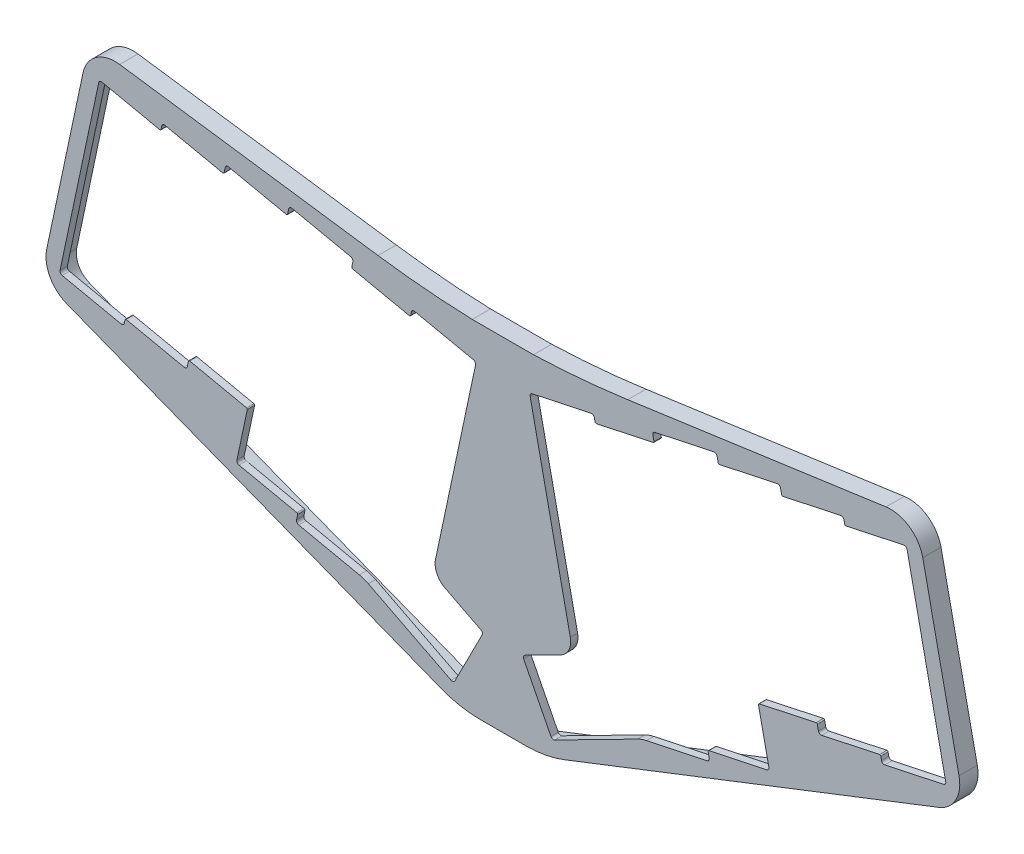
SolidWorks part; units mm, degrees
ref_plane "Front Plane" through (0, 0, 0) normal (0, 0, 1) x (1, 0, 0)
ref_plane "Top Plane" through (0, 0, 0) normal (0, 1, 0) x (1, 0, 0)
ref_plane "Right Plane" through (0, 0, 0) normal (1, 0, 0) x (0, 0, -1)
sketch "Model" plane through (0, 0, 0) normal (0, 0, 1) x (1, 0, 0)
  line L0 (154.4838, -20.4293) -> (153.8335, -20.5675)
  line L1 (132.561, -4.6423) -> (132.9485, -6.4654)
  line L2 (96.3912, -4.6423) -> (96.0037, -6.4654)
  line L3 (74.4684, -20.4293) -> (75.1187, -20.5675)
  line L4 (190.9006, 56.3705) -> (190.5991, 57.7888)
  line L5 (189.7096, 58.3664) -> (173.8636, 54.9983)
  line L6 (207.1024, 59.5076) -> (191.2564, 56.1394)
  line L7 (173.2063, 56.6477) -> (173.5078, 55.2294)
  line L8 (156.1773, 53.7948) -> (172.3167, 57.2253)
  line L9 (155.5996, 52.9053) -> (155.9011, 51.4869)
  line L10 (140.1175, 47.8253) -> (155.67, 51.1311)
  line L11 (139.5641, 48.9856) -> (139.7617, 48.0564)
  line L12 (122.5352, 46.1328) -> (138.6746, 49.5633)
  line L13 (130.551, 4.8138) -> (121.9574, 45.2436)
  line L14 (132.561, -4.6423) -> (130.551, 4.8138)
  line L15 (120.4913, -16.9719) -> (130.3277, -11.96)
  line L16 (127.6544, -32.6822) -> (120.1636, -17.9806)
  line L17 (151.3727, -21.4389) -> (128.6628, -33.0102)
  line L18 (154.4838, -20.4293) -> (170.4653, -17.0323)
  line L19 (171.043, -16.1428) -> (170.7415, -14.7244)
  line L20 (186.8186, -11.0005) -> (170.9726, -14.3686)
  line L21 (187.3963, -10.1109) -> (184.5479, 3.2897)
  line L22 (200.3315, 6.9513) -> (184.7789, 3.6455)
  line L23 (200.6873, 6.7203) -> (200.9888, 5.3019)
  line L24 (218.2776, 6.9321) -> (218.0801, 7.8614)
  line L25 (201.8783, 4.7243) -> (217.7243, 8.0924)
  line L26 (227.8628, 8.2028) -> (219.1672, 6.3544)
  line L27 (235.3066, 9.785) -> (227.8628, 8.2028)
  line L28 (38.0516, 56.3705) -> (38.3531, 57.7888)
  line L29 (39.2426, 58.3664) -> (55.0886, 54.9983)
  line L30 (4.5609, 61.1377) -> (20.4069, 57.7696)
  line L31 (20.9602, 58.9299) -> (20.7627, 58.0006)
  line L32 (21.8498, 59.5076) -> (37.6958, 56.1394)
  line L33 (55.7459, 56.6477) -> (55.4444, 55.2294)
  line L34 (72.7749, 53.7948) -> (56.6354, 57.2253)
  line L35 (73.3526, 52.9053) -> (73.0511, 51.4869)
  line L36 (88.8347, 47.8253) -> (73.2821, 51.1311)
  line L37 (89.388, 48.9856) -> (89.1905, 48.0564)
  line L38 (106.417, 46.1328) -> (90.2776, 49.5633)
  line L39 (98.4012, 4.8138) -> (106.9948, 45.2436)
  line L40 (96.3912, -4.6423) -> (98.4012, 4.8138)
  line L41 (108.4608, -16.9719) -> (98.6245, -11.96)
  line L42 (101.2978, -32.6822) -> (108.7886, -17.9806)
  line L43 (77.5795, -21.4389) -> (100.2893, -33.0102)
  line L44 (74.4684, -20.4293) -> (58.4869, -17.0323)
  line L45 (57.9092, -16.1428) -> (58.2107, -14.7244)
  line L46 (42.1336, -11.0005) -> (57.9796, -14.3686)
  line L47 (41.5559, -10.1109) -> (44.4043, 3.2897)
  line L48 (28.6207, 6.9513) -> (44.1732, 3.6455)
  line L49 (28.2649, 6.7203) -> (27.9634, 5.3019)
  line L50 (10.6745, 6.9321) -> (10.872, 7.8614)
  line L51 (27.0739, 4.7243) -> (11.2279, 8.0924)
  line L52 (1.0894, 8.2028) -> (9.785, 6.3544)
  line L53 (-6.3544, 9.785) -> (1.0894, 8.2028)
  line L54 (-6.861, 11.0092) -> (-6.9321, 10.6744)
  line L55 (3.6714, 60.5601) -> (-6.861, 11.0092)
  line L56 (120.9761, -36.0417) -> (122.177, -36.0417)
  line L57 (120.9761, -36.4417) -> (122.177, -36.4417)
  line L58 (107.9761, -36.0417) -> (106.7752, -36.0417)
  line L59 (107.9761, -36.4417) -> (106.7752, -36.4417)
  line L60 (119.4761, -36.0417) -> (120.9761, -36.0417)
  line L61 (119.4761, -36.4417) -> (120.9761, -36.4417)
  line L62 (109.4761, -36.0417) -> (107.9761, -36.0417)
  line L63 (109.4761, -36.4417) -> (107.9761, -36.4417)
  line L64 (130.1088, -33.2876) -> (123.8474, -35.7278)
  line L65 (130.2541, -33.6603) -> (123.9926, -36.1005)
  line L66 (98.8433, -33.2876) -> (105.1048, -35.7278)
  line L67 (98.6981, -33.6603) -> (104.9596, -36.1005)
  line L68 (114.4761, -36.0417) -> (119.4761, -36.0417)
  line L69 (114.4761, -36.4417) -> (119.4761, -36.4417)
  line L70 (114.4761, -36.0417) -> (109.4761, -36.0417)
  line L71 (114.4761, -36.4417) -> (109.4761, -36.4417)
  line L72 (108.1261, 52.202) -> (120.8261, 52.202)
  line L73 (108.1261, 52.602) -> (120.8261, 52.602)
  line L74 (106.0842, 55.5642) -> (122.868, 55.5642)
  line L75 (80.2395, 57.8151) -> (9.4178, 67.7684)
  line L76 (-0.6381, 60.7272) -> (-10.5878, 13.9175)
  line L77 (-5.0525, 3.6606) -> (97.6451, -36.3623)
  line L78 (108.1754, -38.3417) -> (114.4761, -38.3417)
  line L79 (114.4761, -38.3417) -> (120.7768, -38.3417)
  line L80 (131.3071, -36.3623) -> (234.0046, 3.6606)
  line L81 (239.5399, 13.9175) -> (229.5902, 60.7272)
  line L82 (219.5343, 67.7684) -> (148.7127, 57.8151)
  line L83 (130.1088, -33.2876) -> (232.8064, 6.7354)
  line L84 (236.312, 13.2314) -> (226.3623, 60.0411)
  line L85 (219.9936, 64.5005) -> (149.1719, 54.5472)
  line L86 (130.2541, -33.6603) -> (232.9516, 6.3627)
  line L87 (236.7033, 13.3146) -> (226.7536, 60.1242)
  line L88 (219.9379, 64.8966) -> (149.1163, 54.9433)
  line L89 (79.7802, 54.5472) -> (8.9586, 64.5005)
  line L90 (2.5898, 60.0411) -> (-7.3599, 13.2314)
  line L91 (-3.8542, 6.7354) -> (98.8433, -33.2876)
  line L92 (79.8359, 54.9433) -> (9.0142, 64.8966)
  line L93 (2.1986, 60.1242) -> (-7.7511, 13.3146)
  line L94 (-3.9994, 6.3627) -> (98.6981, -33.6603)
  line L95 (224.3913, 61.1377) -> (208.5453, 57.7696)
  line L96 (207.9919, 58.9299) -> (208.1894, 58.0006)
  line L97 (235.8132, 11.0092) -> (235.8843, 10.6744)
  line L98 (225.2808, 60.5601) -> (235.8132, 11.0092)
  line L99 (108.1159, 52.2022) -> (108.1261, 52.202)
  line L100 (120.8261, 52.202) -> (120.8363, 52.2022)
  arc A0 (130.3277, -11.96) -> (132.9485, -6.4654) centre (128.0578, -7.505) ccw
  arc A1 (153.8335, -20.5675) -> (151.3727, -21.4389) centre (155.9126, -30.349) ccw
  arc A2 (96.0037, -6.4654) -> (98.6245, -11.96) centre (100.8944, -7.505) ccw
  arc A3 (77.5795, -21.4389) -> (75.1187, -20.5675) centre (73.0396, -30.349) ccw
  circle A4 centre (210.5718, 3.5051) radius 1
  circle A5 centre (147.4779, 51.4345) radius 1
  circle A6 centre (114.4761, 38.421) radius 1
  circle A7 centre (114.4761, -18.3417) radius 1
  circle A8 centre (81.4742, 51.4345) radius 1
  circle A9 centre (18.3804, 3.5051) radius 1
  circle A10 centre (13.0465, 61.3788) radius 1
  arc A11 (190.5991, 57.7888) -> (189.7096, 58.3664) centre (189.8655, 57.6328) ccw
  arc A12 (173.5078, 55.2294) -> (173.8636, 54.9983) centre (173.8012, 55.2917) ccw
  arc A13 (190.9006, 56.3705) -> (191.2564, 56.1394) centre (191.194, 56.4328) ccw
  arc A14 (155.67, 51.1311) -> (155.9011, 51.4869) centre (155.6077, 51.4246) ccw
  arc A15 (139.7617, 48.0564) -> (140.1175, 47.8253) centre (140.0551, 48.1188) ccw
  arc A16 (173.2063, 56.6477) -> (172.3167, 57.2253) centre (172.4727, 56.4917) ccw
  arc A17 (156.1773, 53.7948) -> (155.5996, 52.9053) centre (156.3332, 53.0612) ccw
  arc A18 (139.5641, 48.9856) -> (138.6746, 49.5633) centre (138.8305, 48.8297) ccw
  arc A19 (122.5352, 46.1328) -> (121.9574, 45.2436) centre (122.6911, 45.3992) ccw
  arc A20 (120.4913, -16.9719) -> (120.1636, -17.9806) centre (120.8318, -17.6401) ccw
  arc A21 (127.6544, -32.6822) -> (128.6628, -33.0102) centre (128.3227, -32.3417) ccw
  arc A22 (170.9726, -14.3686) -> (170.7415, -14.7244) centre (171.035, -14.6621) ccw
  arc A23 (184.7789, 3.6455) -> (184.5479, 3.2897) centre (184.8413, 3.3521) ccw
  arc A24 (200.6873, 6.7203) -> (200.3315, 6.9513) centre (200.3939, 6.6579) ccw
  arc A25 (170.4653, -17.0323) -> (171.043, -16.1428) centre (170.3094, -16.2987) ccw
  arc A26 (186.8186, -11.0005) -> (187.3963, -10.1109) centre (186.6626, -10.2668) ccw
  arc A27 (218.0801, 7.8614) -> (217.7243, 8.0924) centre (217.7867, 7.799) ccw
  arc A28 (200.9888, 5.3019) -> (201.8783, 4.7243) centre (201.7224, 5.4579) ccw
  arc A29 (218.2776, 6.9321) -> (219.1672, 6.3544) centre (219.0113, 7.0881) ccw
  arc A30 (39.2426, 58.3664) -> (38.3531, 57.7888) centre (39.0867, 57.6328) ccw
  arc A31 (55.0886, 54.9983) -> (55.4444, 55.2294) centre (55.151, 55.2917) ccw
  arc A32 (37.6958, 56.1394) -> (38.0516, 56.3705) centre (37.7582, 56.4328) ccw
  arc A33 (20.4069, 57.7696) -> (20.7627, 58.0006) centre (20.4693, 58.063) ccw
  arc A34 (73.0511, 51.4869) -> (73.2821, 51.1311) centre (73.3445, 51.4246) ccw
  arc A35 (88.8347, 47.8253) -> (89.1905, 48.0564) centre (88.8971, 48.1188) ccw
  arc A36 (4.5609, 61.1377) -> (3.6714, 60.5601) centre (4.405, 60.4041) ccw
  arc A37 (21.8498, 59.5076) -> (20.9602, 58.9299) centre (21.6939, 58.7739) ccw
  arc A38 (56.6354, 57.2253) -> (55.7459, 56.6477) centre (56.4795, 56.4917) ccw
  arc A39 (73.3526, 52.9053) -> (72.7749, 53.7948) centre (72.6189, 53.0612) ccw
  arc A40 (90.2776, 49.5633) -> (89.388, 48.9856) centre (90.1216, 48.8297) ccw
  arc A41 (106.9948, 45.2436) -> (106.417, 46.1328) centre (106.2611, 45.3992) ccw
  arc A42 (108.7886, -17.9806) -> (108.4608, -16.9719) centre (108.1204, -17.6401) ccw
  arc A43 (100.2893, -33.0102) -> (101.2978, -32.6822) centre (100.6295, -32.3417) ccw
  arc A44 (58.2107, -14.7244) -> (57.9796, -14.3686) centre (57.9172, -14.6621) ccw
  arc A45 (44.4043, 3.2897) -> (44.1732, 3.6455) centre (44.1109, 3.3521) ccw
  arc A46 (28.6207, 6.9513) -> (28.2649, 6.7203) centre (28.5583, 6.6579) ccw
  arc A47 (57.9092, -16.1428) -> (58.4869, -17.0323) centre (58.6428, -16.2987) ccw
  arc A48 (41.5559, -10.1109) -> (42.1336, -11.0005) centre (42.2895, -10.2668) ccw
  arc A49 (11.2279, 8.0924) -> (10.872, 7.8614) centre (11.1655, 7.799) ccw
  arc A50 (27.0739, 4.7243) -> (27.9634, 5.3019) centre (27.2298, 5.4579) ccw
  arc A51 (9.785, 6.3544) -> (10.6745, 6.9321) centre (9.9409, 7.0881) ccw
  arc A52 (-6.9321, 10.6744) -> (-6.3544, 9.785) centre (-6.1985, 10.5186) ccw
  arc A53 (122.177, -36.0417) -> (123.8474, -35.7278) centre (122.177, -31.4417) ccw
  arc A54 (122.177, -36.4417) -> (123.9926, -36.1005) centre (122.177, -31.4417) ccw
  arc A55 (105.1048, -35.7278) -> (106.7752, -36.0417) centre (106.7752, -31.4417) ccw
  arc A56 (104.9596, -36.1005) -> (106.7752, -36.4417) centre (106.7752, -31.4417) ccw
  circle A57 centre (215.9057, 61.3788) radius 1
  arc A58 (208.1894, 58.0006) -> (208.5453, 57.7696) centre (208.4829, 58.063) ccw
  arc A59 (225.2808, 60.5601) -> (224.3913, 61.1377) centre (224.5472, 60.4041) ccw
  arc A60 (207.9919, 58.9299) -> (207.1024, 59.5076) centre (207.2583, 58.7739) ccw
  arc A61 (235.3066, 9.785) -> (235.8843, 10.6744) centre (235.1507, 10.5186) ccw
  arc A62 (80.2395, 57.8151) -> (106.0842, 55.5642) centre (114.4761, 301.421) ccw
  arc A63 (9.4178, 67.7684) -> (-0.6381, 60.7272) centre (8.1653, 58.856) ccw
  arc A64 (-10.5878, 13.9175) -> (-5.0525, 3.6606) centre (-1.7844, 12.0463) ccw
  arc A65 (97.6451, -36.3623) -> (108.1754, -38.3417) centre (108.1754, -9.3417) ccw
  arc A66 (120.7768, -38.3417) -> (131.3071, -36.3623) centre (120.7768, -9.3417) ccw
  arc A67 (234.0046, 3.6606) -> (239.5399, 13.9175) centre (230.7366, 12.0463) ccw
  arc A68 (229.5902, 60.7272) -> (219.5343, 67.7684) centre (220.7869, 58.856) ccw
  arc A69 (122.868, 55.5642) -> (148.7127, 57.8151) centre (114.4761, 301.421) ccw
  arc A70 (232.8064, 6.7354) -> (236.312, 13.2314) centre (230.7366, 12.0463) ccw
  arc A71 (226.3623, 60.0411) -> (219.9936, 64.5005) centre (220.7869, 58.856) ccw
  arc A72 (120.8363, 52.2022) -> (149.1719, 54.5472) centre (114.4761, 301.421) ccw
  arc A73 (232.9516, 6.3627) -> (236.7033, 13.3146) centre (230.7366, 12.0463) ccw
  arc A74 (226.7536, 60.1242) -> (219.9379, 64.8966) centre (220.7869, 58.856) ccw
  arc A75 (120.8261, 52.602) -> (149.1163, 54.9433) centre (114.4761, 301.421) ccw
  arc A76 (79.7802, 54.5472) -> (108.1159, 52.2022) centre (114.4761, 301.421) ccw
  arc A77 (8.9586, 64.5005) -> (2.5898, 60.0411) centre (8.1653, 58.856) ccw
  arc A78 (-7.3599, 13.2314) -> (-3.8542, 6.7354) centre (-1.7844, 12.0463) ccw
  arc A79 (79.8359, 54.9433) -> (108.1261, 52.602) centre (114.4761, 301.421) ccw
  arc A80 (9.0142, 64.8966) -> (2.1986, 60.1242) centre (8.1653, 58.856) ccw
  arc A81 (-7.7511, 13.3146) -> (-3.9994, 6.3627) centre (-1.7844, 12.0463) ccw
extrude "Boss-Extrude1" add sketch "Model" along normal blind 2 contours A69 L74 A62 L75 A63 L76 A64 L77 A65 L78 L79 A66 L80 A67 L81 A68 L82 A81 L93 A80 L92 A79 L73 A75 L88 A74 L87 A73 L86 L65 A54 L57 L61 L69 L71 L63 L59 A56 L67 L94 | A9 | A10 | A7 | A6 | A5 | A57 | A4 | A8 | L90 A78 L91 L66 A55 L58 L62 L70 L68 L60 L56 A53 L64 L83 A70 L84 A71 L85 A72 L100 L72 L99 A76 L89 A77 A4 A5 A6 A7 A8 A9 A10 A52 L54 L55 A36 L30 A33 L31 A37 L32 A32 L28 | L93 A81 L94 L67 A56 L59 L63 L71 L69 L61 L57 A54 L65 L86 A73 L87 A74 L88 A75 L73 A79 L92 A80 A78 L90 A77 L89 A76 L99 L72 L100 A72 L85 A71 L84 A70 L83 L64 A53 L56 L60 L68 L70 L62 L58 A55 L66 L91 region at (114.4761, 12.873, 0) region at (120.2261, -36.1768, 0) region at (114.4761, 52.8432, 0) region at (210.5718, 3.5051, 0) region at (147.4779, 51.4345, 0) region at (114.4761, 38.421, 0) region at (114.4761, -18.3417, 0) region at (81.4742, 51.4345, 0) region at (18.3804, 3.5051, 0) region at (13.0465, 61.3788, 0) region at (215.9057, 61.3788, 0)
extrude "Boss-Extrude2" add sketch "Model<6>" against normal blind 3 contours L93 A81 L94 L67 A56 L59 L63 L71 L69 L61 L57 A54 L65 L86 A73 L87 A74 L88 A75 L73 A79 L92 A80 A78 L90 A77 L89 A76 L99 L72 L100 A72 L85 A71 L84 A70 L83 L64 A53 L56 L60 L68 L70 L62 L58 A55 L66 L91 | A69 L74 A62 L75 A63 L76 A64 L77 A65 L78 L79 A66 L80 A67 L81 A68 L82 A81 L93 A80 L92 A79 L73 A75 L88 A74 L87 A73 L86 L65 A54 L57 L61 L69 L71 L63 L59 A56 L67 L94 region at (120.2261, -36.1768, 0) region at (114.4761, 52.8432, 0)
sketch "Model<6>" plane through (0, 0, 0) normal (0, 0, 1) x (1, 0, 0) same geometry as "Model"
